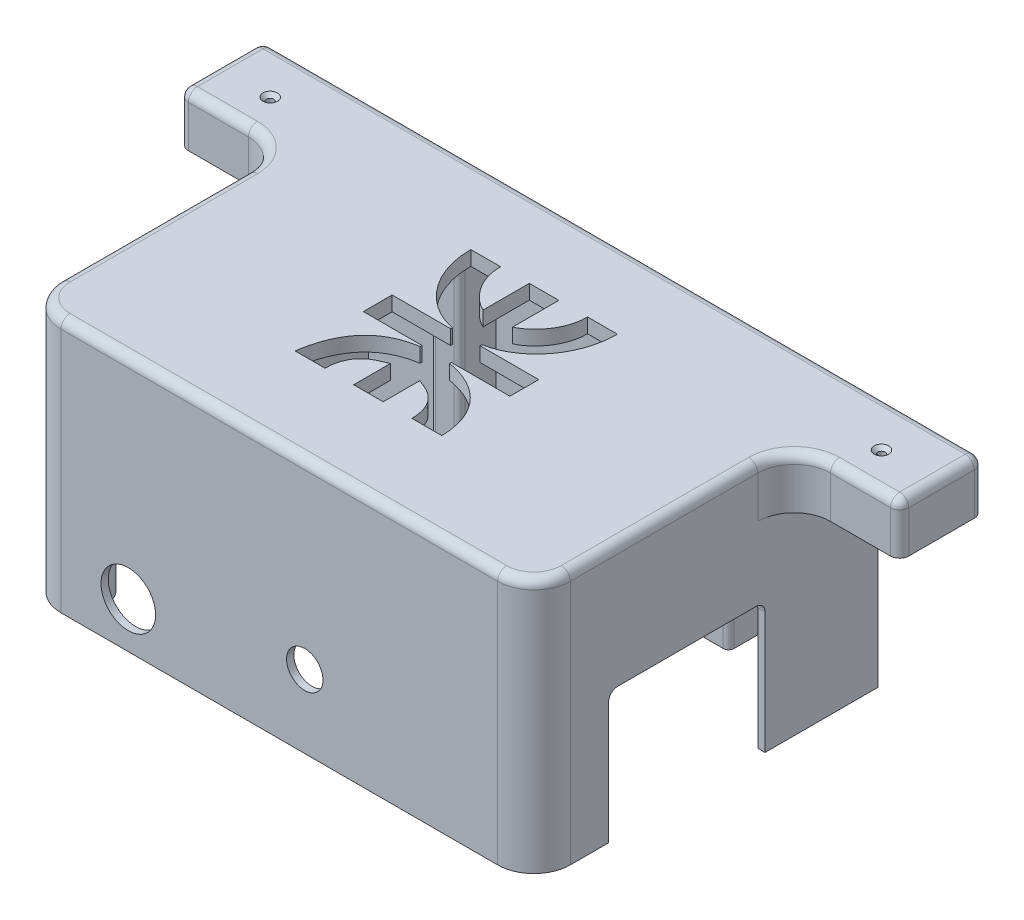
SolidWorks part; units mm, degrees
ref_plane "Alzado" through (0, 0, 0) normal (0, 0, 1) x (1, 0, 0)
ref_plane "Planta" through (0, 0, 0) normal (0, 1, 0) x (1, 0, 0)
ref_plane "Vista lateral" through (0, 0, 0) normal (1, 0, 0) x (0, 0, -1)
sketch "Croquis1" plane through (0, 0, 0) normal (0, 1, 0) x (1, 0, 0)
  line L0 (-70, -35.8212) -> (70, -35.8212)
  line L2 (-70, -35.8212) -> (-70, 35.6788)
  line L3 (-70, 35.6788) -> (-99, 35.6788)
  line L4 (-99, 35.6788) -> (-99, 58.6788)
  line L5 (0, -55) -> (0, 55) construction
  line L6 (99, 35.6788) -> (99, 58.6788)
  line L7 (70, 35.6788) -> (99, 35.6788)
  line L8 (70, -35.8212) -> (70, 35.6788)
  line L9 (-99, 58.6788) -> (99, 58.6788)
  point P6 (-70, -35.8212)
  point P7 (70, -35.8212)
extrude "Saliente-Extruir1" add sketch "Croquis1" along normal blind 70
sketch "Croquis2" plane through (0, 70, 0) normal (0, 1, 0) x (1, 0, 0)
  line L0 (-70, 35.6788) -> (-70, 58.6788)
  line L1 (99, 58.6788) -> (-99, 58.6788) construction
  line L2 (-70, 58.6788) -> (-99, 58.6788)
  line L3 (-99, 58.6788) -> (-99, 35.6788)
  line L4 (-99, 35.6788) -> (-70, 35.6788)
  line L5 (0, -38.5) -> (0, 38.5) construction
  line L6 (99, 58.6788) -> (99, 35.6788)
  line L7 (70, 58.6788) -> (99, 58.6788)
  line L8 (70, 35.6788) -> (70, 58.6788)
  line L9 (99, 35.6788) -> (70, 35.6788)
extrude "Cortar-Extruir1" cut sketch "Croquis2" along normal blind 56 from surface starting at plane "Planta"
sketch "Croquis3" plane through (0, 0, 0) normal (0, -1, 0) x (1, 0, 0)
  line L0 (-70, 35.8212) -> (-70, 33.8212) construction
  line L1 (-70, -58.6788) -> (-70, 35.8212) construction
  line L2 (-70, 35.8212) -> (-68, 35.8212) construction
  line L3 (-70, 35.8212) -> (70, 35.8212) construction
  line L4 (0, -38.5) -> (0, 38.5) construction
  line L5 (70, 35.8212) -> (68, 35.8212) construction
  line L6 (70, 35.8212) -> (70, 33.8212) construction
  line L7 (-70, -58.6788) -> (-70, -56.6788) construction
  line L8 (-70, -56.6788) -> (-68, -56.6788) construction
  line L9 (-68, 33.8212) -> (-68, -56.6788)
  line L10 (-68, -56.6788) -> (68, -56.6788)
  line L11 (68, -56.6788) -> (68, 33.8212)
  line L12 (68, 33.8212) -> (-68, 33.8212)
extrude "Cortar-Extruir2" cut sketch "Croquis3" against normal blind 66
fillet "Redondeo5" radius 10 2 edges at (70, 63, -35.6788) (-70, 63, -35.6788)
fillet "Redondeo13" radius 2.5 4 edges at (99, 63, -35.6788) (99, 63, -58.6788) (-99, 63, -58.6788) (-99, 63, -35.6788)
fillet "Redondeo14" radius 10 2 edges at (-68, 33, 33.8212) (68, 33, 33.8212)
fillet "Redondeo15" radius 10 2 edges at (70, 35, 35.8212) (-70, 35, 35.8212)
sketch "Croquis7" plane through (0, 0, -58.6788) normal (0, 0, -1) x (-1, 0, 0)
  line L0 (-7.5, 0) -> (7.5, 0)
  line L1 (51.975, 0) -> (-51.975, 0) construction
  line L2 (-7.5, 0) -> (-7.5, 13)
  line L3 (-7.5, 13) -> (7.5, 13)
  line L4 (7.5, 13) -> (7.5, 0)
  point P6 (0, 0)
  line M9 (-70, 0) -> (70, 0)
extrude "Cortar-Extruir4" cut sketch "Croquis7" against normal up to next from surface contours L4 L3 L2 M9 region at (0, 6.5, -58.6788) starting at face at (0, 45.5, -58.6788)
sketch "Croquis8" plane through (-70, 0, 0) normal (-1, 0, 0) x (0, 0, 1)
  line L0 (-58.6788, 0) -> (-24.6788, 0) construction
  line L2 (-27.6788, 0) -> (-27.6788, 36)
  line L4 (15.3212, 36) -> (15.3212, 0)
  line L7 (15.3212, 0) -> (-27.6788, 0)
  line L9 (15.3212, 36) -> (-27.6788, 36)
extrude "Cortar-Extruir5" cut sketch "Croquis8" against normal up to surface (140 mm away) from surface up to face at (70, 42, -19.5121) starting at face at (-70, 42, -19.5121)
sketch "Croquis9" plane through (0, 0, 35.8212) normal (0, 0, 1) x (1, 0, 0)
  line L0 (-70, 2.1351) -> (-53, 2.1351) construction
  line L1 (-70, 0) -> (-70, 70) construction
  line L2 (-41.5, 5) -> (-41.5, 12.5) construction
  line L3 (-53, 0) -> (-53, 5) construction
  line L4 (51.975, 0) -> (-51.975, 0) construction
  line L5 (-53, 5) -> (-30, 5) construction
  line L6 (-70, 2.1351) -> (2, 2.1351) construction
  line L7 (2, 0) -> (2, 15) construction
  line L8 (2, 15) -> (12, 15) construction
  line L9 (12, 15) -> (12, 0) construction
  line L10 (7, 15) -> (7, 20) construction
  circle A0 centre (-41.5, 12.5) radius 7.5
  circle A1 centre (7, 20) radius 5
extrude "Cortar-Extruir6" cut sketch "Croquis9" against normal up to surface (2 mm away) up to face at (0, 33, 33.8212)
sketch "Croquis10" plane through (0, 0, 0) normal (0, 1, 0) x (1, 0, 0)
  line L0 (0, -38.5) -> (0, 38.5) construction
  line L1 (56, -21.8212) -> (68, -21.8212)
  line L2 (56, -33.8212) -> (56, -21.8212)
  line L6 (-56, -33.8212) -> (-56, -21.8212)
  line L8 (58, -33.8212) -> (-58, -33.8212) construction
  line L9 (-56, -21.8212) -> (-68, -21.8212)
  line L10 (-68, -23.8212) -> (-68, -15.3212) construction
  circle A0 centre (-62, -27.8212) radius 1
  arc A4 (-56, -33.8212) -> (-68, -21.8212) centre (-57.6744, -23.4956) cw
  circle A5 centre (62, -27.8212) radius 1
  arc A6 (56, -33.8212) -> (68, -21.8212) centre (57.6744, -23.4956) ccw
extrude "Saliente-Extruir8" add sketch "Croquis10" along normal up to surface (66 mm away) contours A4 L6 L9 A0 | A0 | L2 A6 L1 A5 | A5 region at (62, 0, 21.9928) region at (-64.9497, 0, 30.771) region at (-62, 0, 27.8212) region at (62, 0, 27.8212) up to face at (0, 66, 1.0116)
extrude "Cortar-Extruir7" cut sketch "Croquis10<4>" along normal blind 10 contours A5 | A0
sketch "Croquis10<4>" plane through (0, 0, 0) normal (0, 1, 0) x (1, 0, 0) same geometry as "Croquis10"
fillet "Redondeo18" radius 5 2 edges at (56, 33, 21.8212) (-56, 33, 21.8212)
sketch "Croquis12" plane through (0, 0, 0) normal (0, 1, 0) x (1, 0, 0)
  line L0 (-99, 58.6788) -> (-37, 58.6788) construction
  line L1 (-96.5, 58.6788) -> (-99, 58.6788) construction
  line L2 (-7.5, 58.6788) -> (-70, 58.6788) construction
  line L3 (-37, 58.6788) -> (-37, 50.6788) construction
  line L4 (-37, 56.6788) -> (-41, 56.6788) construction
  line L5 (-68, 56.6788) -> (68, 56.6788) construction
  line L6 (-41, 56.6788) -> (-41, 46.6788)
  line L7 (-41, 46.6788) -> (-32.997, 46.6788)
  line L8 (-32.997, 46.6788) -> (-32.997, 56.6788)
  line L9 (-68, 56.6788) -> (-7.5, 56.6788) construction
  line L10 (-32.997, 56.6788) -> (-41, 56.6788)
  line L11 (0, -38.5) -> (0, 38.5) construction
  line L12 (37, 56.6788) -> (41, 56.6788) construction
  line L13 (37, 58.6788) -> (37, 50.6788) construction
  line L14 (99, 58.6788) -> (37, 58.6788) construction
  line L15 (32.997, 56.6788) -> (41, 56.6788)
  line L16 (32.997, 46.6788) -> (32.997, 56.6788)
  line L17 (41, 46.6788) -> (32.997, 46.6788)
  line L18 (41, 56.6788) -> (41, 46.6788)
  circle A0 centre (-37, 50.6788) radius 1
  circle A1 centre (37, 50.6788) radius 1
extrude "Saliente-Extruir9" add sketch "Croquis12" along normal up to surface (66 mm away) contours L8 L10 L6 L7 A0 | A0 | L18 L15 L16 L17 A1 | A1 region at (-36.9984, 0, -51.7196) region at (36.9984, 0, -51.7196) region at (-37, 0, -50.6788) region at (37, 0, -50.6788) up to face at (0, 66, 9.3141)
extrude "Cortar-Extruir8" cut sketch "Croquis12<3>" along normal blind 10 contours A0 | A1
sketch "Croquis12<3>" plane through (0, 0, 0) normal (0, 1, 0) x (1, 0, 0) same geometry as "Croquis12"
fillet "Redondeo19" radius 1.5 4 edges at (-32.997, 33, -46.6788) (-41, 33, -46.6788) (32.997, 33, -46.6788) (41, 33, -46.6788)
sketch "Croquis13" plane through (0, 70, 0) normal (0, 1, 0) x (1, 0, 0)
  line L0 (-96.5, 35.6788) -> (-100.407, 35.6788) construction
  line L1 (-99, 38.1788) -> (-99, 35.6788) construction
  line L2 (-99, 35.6788) -> (-99, 45.6788) construction
  line L3 (-99, 56.1788) -> (-99, 38.1788) construction
  line L4 (-99, 45.6788) -> (-84, 45.6788) construction
  line L5 (0, -38.5) -> (0, 38.5) construction
  line L6 (99, 45.6788) -> (84, 45.6788) construction
  line L7 (99, 35.6788) -> (99, 45.6788) construction
  line L8 (99, 38.1788) -> (99, 35.6788) construction
  line L9 (96.5, 35.6788) -> (100.407, 35.6788) construction
  circle A0 centre (-84, 45.6788) radius 1
  circle A1 centre (84, 45.6788) radius 1
extrude "Cortar-Extruir9" cut sketch "Croquis13" against normal up to next
fillet "Redondeo20" radius 2.5 16 edges at (98.2678, 70, -57.9465) (99, 70, -47.1788) (98.2678, 70, -36.411) (88.25, 70, -35.6788) (72.9289, 70, -32.7498) (70, 70, 0.0712) (67.0711, 70, 32.8923) (0, 70, 35.8212) (-67.0711, 70, 32.8923) (-70, 70, 0.0712) (-72.9289, 70, -32.7498) (-88.25, 70, -35.6788) (-98.2678, 70, -36.411) (-99, 70, -47.1788) (-98.2678, 70, -57.9465) (0, 70, -58.6788)
chamfer "Chaflán1" distance 1 angle 45 2 edges at (84, 70, -46.6788) (-84, 70, -44.6788)
sketch "Croquis14" plane through (0, 70, 0) normal (0, 1, 0) x (1, 0, 0)
  line L0 (-20.1468, 15.0144) -> (20.1379, 15.0144) construction
  line L1 (-20.1468, 15.3402) -> (20.1379, 7.4225) construction
  line L2 (-20.1468, 36.9565) -> (-11.9507, 36.9565)
  line L3 (-4.0572, 36.9565) -> (-4.0572, 24.2899)
  line L4 (-4.0572, 36.9565) -> (-0.0045, 36.9565)
  line L5 (-4.0572, 15.8581) -> (-4.0572, 15.3402)
  line L6 (-4.0572, 15.3402) -> (-20.1468, 15.3402)
  line L7 (-20.1468, 15.3402) -> (-20.1468, 7.4225)
  line L8 (-20.1468, 7.4225) -> (-4.0572, 7.4225)
  line L9 (-4.0572, 7.4225) -> (-4.0572, 6.9139)
  line L10 (4.0521, -11.3155) -> (-4.0611, -11.3155)
  line L11 (-4.0611, -11.3155) -> (-4.0611, -1.2576)
  line L12 (-20.1468, -11.3155) -> (-12.2332, -11.3155)
  line L13 (-11.9507, -11.3155) -> (-12.2332, -11.3155)
  line L14 (4.0483, 7.4225) -> (4.0483, 6.9139)
  line L15 (4.0483, 15.8581) -> (4.0483, 15.3402)
  line L16 (4.0521, -11.3155) -> (4.0521, -1.2576)
  line L17 (20.1379, -11.3155) -> (12.2243, -11.3155)
  line L18 (20.1379, 7.4225) -> (4.0483, 7.4225)
  line L19 (20.1379, 15.3402) -> (20.1379, 7.4225)
  line L20 (4.0483, 15.3402) -> (20.1379, 15.3402)
  line L21 (20.1379, 36.9565) -> (11.9418, 36.9565)
  line L22 (4.0483, 36.9565) -> (4.0483, 24.2899)
  line L23 (4.0483, 36.9565) -> (-0.0045, 36.9565)
  line L24 (12.2243, -11.3155) -> (11.9418, -11.3155)
  line L25 (20.1379, 15.3402) -> (-20.1468, 7.4225) construction
  line L26 (0, 58.6788) -> (0, -35.9077) construction
  line L27 (-96.5, 58.6788) -> (96.5, 58.6788) construction
  line L28 (0, -38.5) -> (0, 38.5) construction
  spline S0 degree 3 poles (-20.1468, 36.9565) (-20.1986, 25.9232) (-12.5798, 17.333) (-4.0572, 15.8581) knots 0 0 0 0 1 1 1 1
  spline S1 degree 3 poles (-4.0572, 24.2899) (-6.6958, 25.2563) (-12.0748, 30.0997) (-11.9507, 36.9565) knots 0 0 0 0 1 1 1 1
  spline S2 degree 2 poles (-4.0572, 6.9139) (-17.8879, 4.7551) (-20.1468, -11.3155) knots 0 0 0 1 1 1
  spline S3 degree 3 poles (-4.0611, -1.2576) (-5.3686, -1.9436) (-11.8858, -3.0723) (-11.9507, -11.3155) knots 0 0 0 0 1 1 1 1
  spline S4 degree 3 poles (4.0521, -1.2576) (5.3597, -1.9436) (11.8768, -3.0723) (11.9418, -11.3155) knots 0 0 0 0 1 1 1 1
  spline S5 degree 3 poles (4.0483, 6.9139) (13.2688, 5.4747) (20.0634, -0.9824) (20.1379, -11.3155) knots 0 0 0 0 1 1 1 1
  spline S6 degree 3 poles (20.1379, 36.9565) (20.1897, 25.9232) (12.5709, 17.333) (4.0483, 15.8581) knots 0 0 0 0 1 1 1 1
  spline S7 degree 3 poles (4.0483, 24.2899) (6.6869, 25.2563) (12.0659, 30.0997) (11.9418, 36.9565) knots 0 0 0 0 1 1 1 1
  point P2 (-0.0045, 11.3814)
  point P28 (-0.0045, -11.3155)
  point P41 (0.0299, 15.0144)
extrude "Cortar-Extruir10" cut sketch "Croquis14" against normal up to next
fillet "Redondeo21" radius 2.5 4 edges at (-69, 36, 15.3212) (-69, 36, -27.6788) (69, 36, -27.6788) (69, 36, 15.3212)
